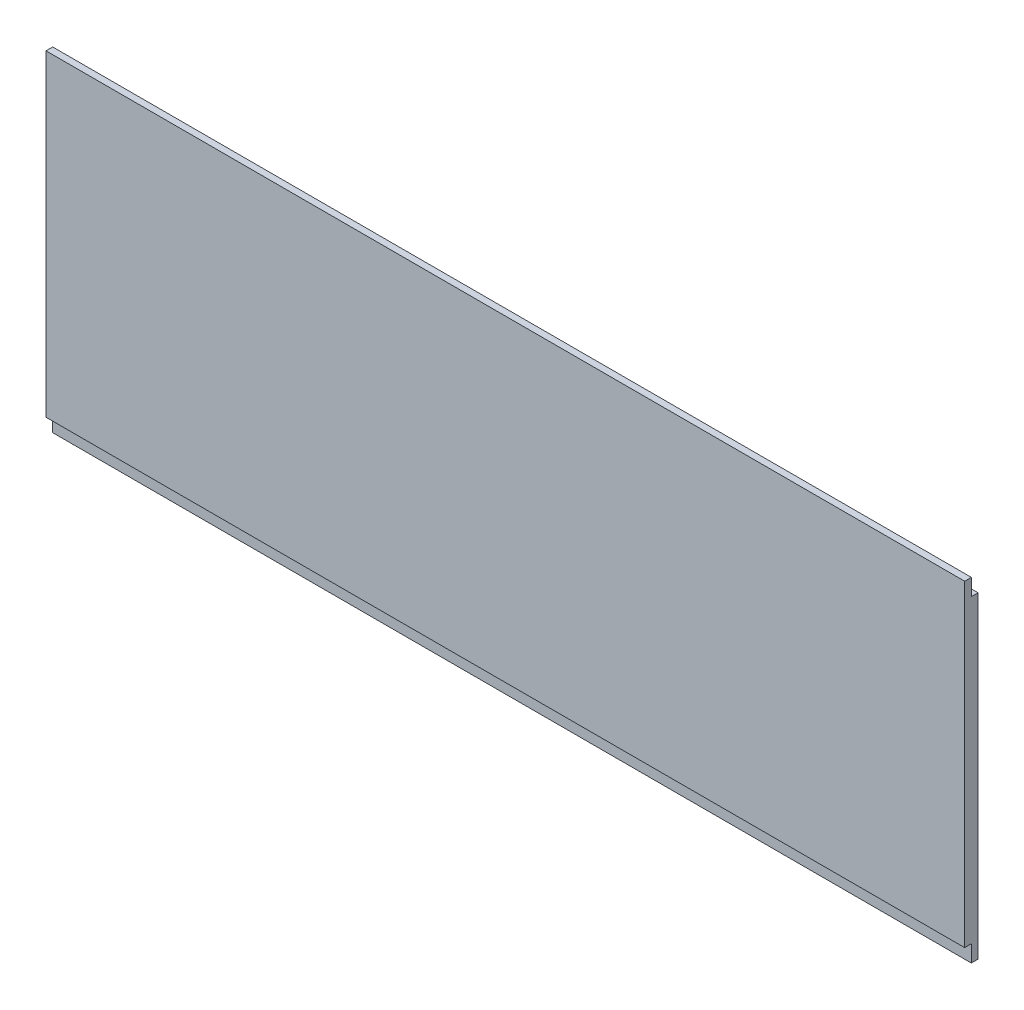
SolidWorks part; units mm, degrees
ref_plane "Спереди" through (0, 0, 0) normal (0, 0, 1) x (1, 0, 0)
ref_plane "Сверху" through (0, 0, 0) normal (0, 1, 0) x (1, 0, 0)
ref_plane "Справа" through (0, 0, 0) normal (1, 0, 0) x (0, 0, -1)
sketch "Эскиз1" plane through (0, 0, 0) normal (1, 0, 0) x (0, 0, -1)
  line L0 (0, 0) -> (0, 190)
  line L1 (0, 190) -> (-4, 190)
  line L2 (-4, 190) -> (-4, 200)
  line L3 (-4, 200) -> (-8, 200)
  line L4 (-8, 200) -> (-8, 10)
  line L5 (-8, 10) -> (-4, 10)
  line L6 (-4, 10) -> (-4, 0)
  line L7 (-4, 0) -> (0, 0)
  point P3 (0, 0)
extrude "Бобышка-Вытянуть1" add sketch "Эскиз1" along normal blind 550
